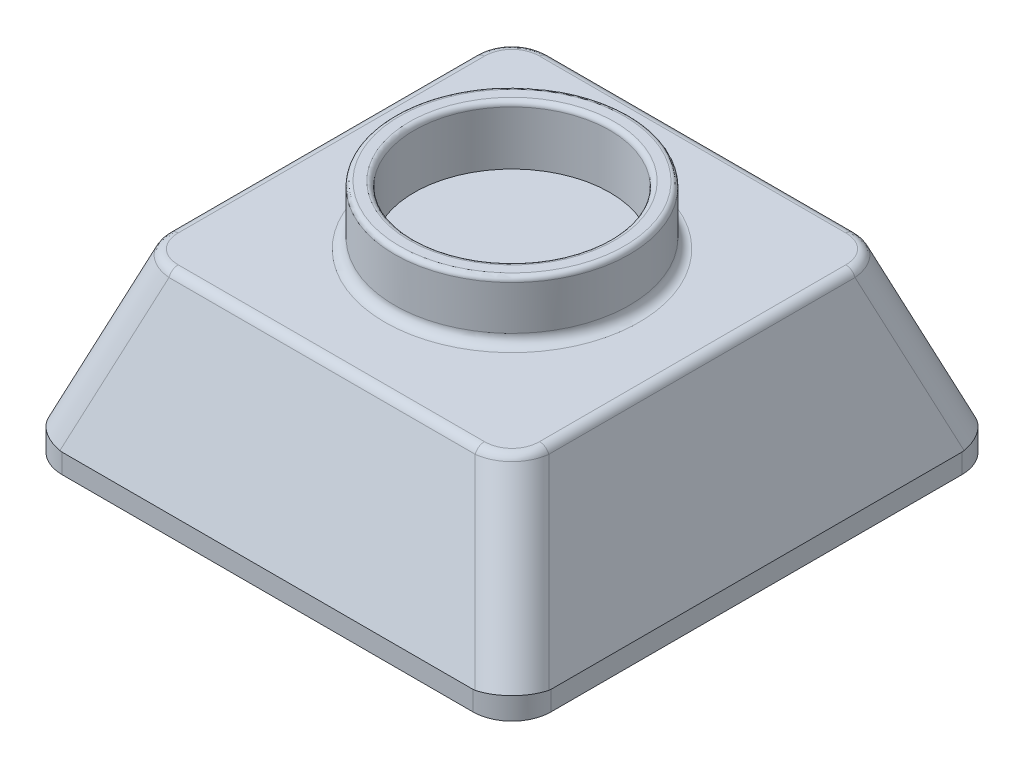
SolidWorks part; units mm, degrees
material "Commercial Bronze, UNS C22000 (90-10 Bronze)"
ref_plane "Front Plane" through (0, 0, 0) normal (0, 0, 1) x (1, 0, 0)
ref_plane "Top Plane" through (0, 0, 0) normal (0, 1, 0) x (1, 0, 0)
ref_plane "Right Plane" through (0, 0, 0) normal (1, 0, 0) x (0, 0, -1)
sketch "Sketch1" plane through (0, 0, 0) normal (0, 1, 0) x (1, 0, 0)
  line L1 (-317.5, -317.5) -> (317.5, -317.5)
  line L2 (-317.5, -317.5) -> (-317.5, 317.5)
  line L3 (-317.5, 317.5) -> (317.5, 317.5)
  line L4 (317.5, -317.5) -> (317.5, 317.5)
  line L5 (-317.5, -317.5) -> (317.5, 317.5) construction
  line L6 (-317.5, 317.5) -> (317.5, -317.5) construction
  point P0 (0, 0)
  dimension "D1" = 635
  dimension "D2" = 635
extrude "Boss-Extrude1" add sketch "Sketch1" along normal blind 203.2 draft 20
sketch "Sketch2" plane through (0, 203.2, 0) normal (0, 1, 0) x (1, 0, 0)
  circle A0 centre (0, 0) radius 152.4
  circle A1 centre (0, 0) radius 127
  dimension "D1" = 304.8
  dimension "D2" = 254
extrude "Boss-Extrude2" add sketch "Sketch2" along normal blind 76.2
fillet "Fillet1" radius 50.8 1 edges at (280.5206, 101.6, 280.5206)
fillet "Fillet2" radius 50.8 1 edges at (280.5206, 101.6, -280.5206)
fillet "Fillet3" radius 50.8 1 edges at (-280.5206, 101.6, 280.5206)
fillet "Fillet4" radius 50.8 1 edges at (-280.5206, 101.6, -280.5206)
fillet "Fillet5" radius 12.7 8 edges at (-229.8814, 203.2, -229.8814) (0, 203.2, -243.5412) (229.8814, 203.2, -229.8814) (243.5412, 203.2, 0) (229.8814, 203.2, 229.8814) (0, 203.2, 243.5412) (-229.8814, 203.2, 229.8814) (-243.5412, 203.2, 0)
fillet "Fillet6" radius 6.35 1 edges at (0, 279.4, 152.4)
fillet "Fillet7" radius 6.35 1 edges at (0, 279.4, 127)
fillet "Fillet8" radius 12.7 1 edges at (0, 203.2, -152.4)
sketch "Sketch5" plane through (0, 0, 0) normal (0, -1, 0) x (1, 0, 0)
  line L1 (-317.5, 317.5) -> (317.5, 317.5)
  line L2 (-317.5, 317.5) -> (-317.5, -317.5)
  line L3 (-317.5, -317.5) -> (317.5, -317.5)
  line L4 (317.5, 317.5) -> (317.5, -317.5)
extrude "Boss-Extrude3" add sketch "Sketch5" along normal blind 25.4
fillet "Fillet10" radius 50.8 4 edges at (-317.5, -12.7, 317.5) (-317.5, -12.7, -317.5) (317.5, -12.7, -317.5) (317.5, -12.7, 317.5)
